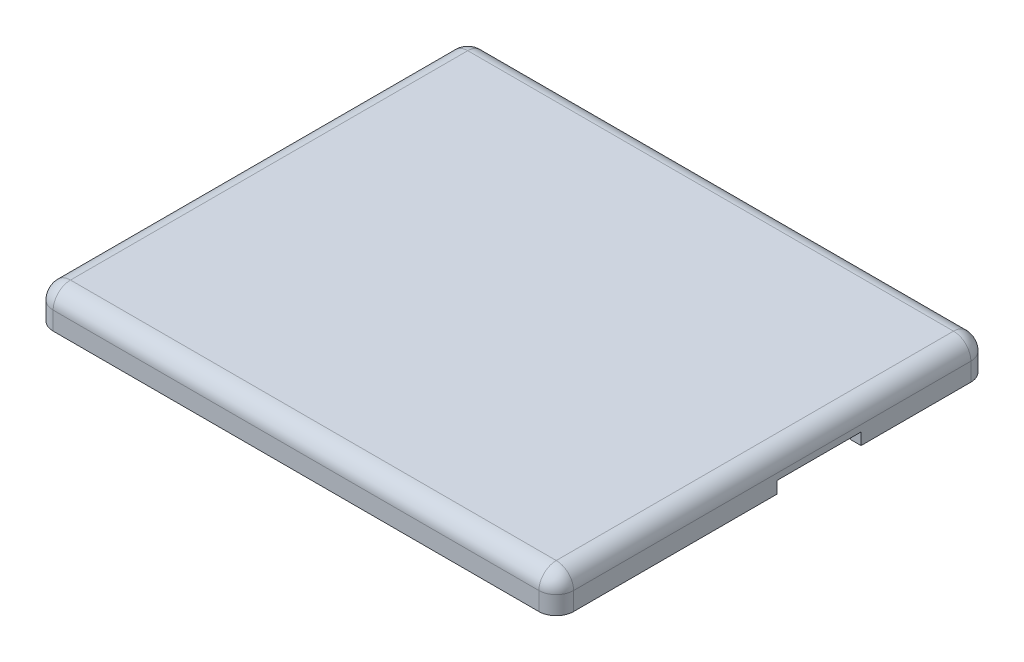
SolidWorks part; units mm, degrees
ref_plane "Front Plane" through (0, 0, 0) normal (0, 0, 1) x (1, 0, 0)
ref_plane "Top Plane" through (0, 0, 0) normal (0, 1, 0) x (1, 0, 0)
ref_plane "Right Plane" through (0, 0, 0) normal (1, 0, 0) x (0, 0, -1)
sketch "Sketch1" plane through (0, 0, 0) normal (0, 1, 0) x (1, 0, 0)
  line L1 (30, -24.9) -> (-30, -24.9)
  line L2 (30, -24.9) -> (30, 24.9)
  line L3 (30, 24.9) -> (-30, 24.9)
  line L4 (-30, -24.9) -> (-30, 24.9)
  line L5 (30, -24.9) -> (-30, 24.9) construction
  line L6 (30, 24.9) -> (-30, -24.9) construction
  point P0 (0, 0)
  dimension "D1" = 60
  dimension "D2" = 49.8
extrude "OuterWalls" add sketch "Sketch1" against normal blind 2
sketch "Sketch2" plane through (0, -2, 0) normal (0, -1, 0) x (-1, 0, 0)
  line L0 (28.8, 23.7) -> (28.8, -23.7)
  line L1 (30, 24.9) -> (-30, 24.9)
  line L2 (30, 24.9) -> (30, -24.9)
  line L3 (30, -24.9) -> (-30, -24.9)
  line L4 (-30, 24.9) -> (-30, -24.9)
  line L5 (28.8, -23.7) -> (-28.8, -23.7)
  line L6 (-28.8, 23.7) -> (-28.8, -23.7)
  line L7 (28.8, 23.7) -> (-28.8, 23.7)
  dimension "D1" = 1.2
extrude "Inner" add sketch "Sketch2" along normal blind 2.1
sketch "Sketch4" plane through (30, 0, 0) normal (1, 0, 0) x (0, 0, -1)
  line L1 (0.5468, -6.0596) -> (10.2373, -6.0596)
  line L2 (0.5468, -6.0596) -> (0.5468, -2.7356)
  line L3 (0.5468, -2.7356) -> (10.2373, -2.7356)
  line L4 (10.2373, -6.0596) -> (10.2373, -2.7356)
extrude "Cut-Extrude1" cut sketch "Sketch4" against normal blind 20
fillet "Fillet1" radius 2 8 edges at (30, 0, 0) (-30, -2.05, 24.9) (-30, -2.05, -24.9) (30, -2.05, -24.9) (30, -2.05, 24.9) (0, 0, 24.9) (-30, 0, 0) (0, 0, -24.9)
